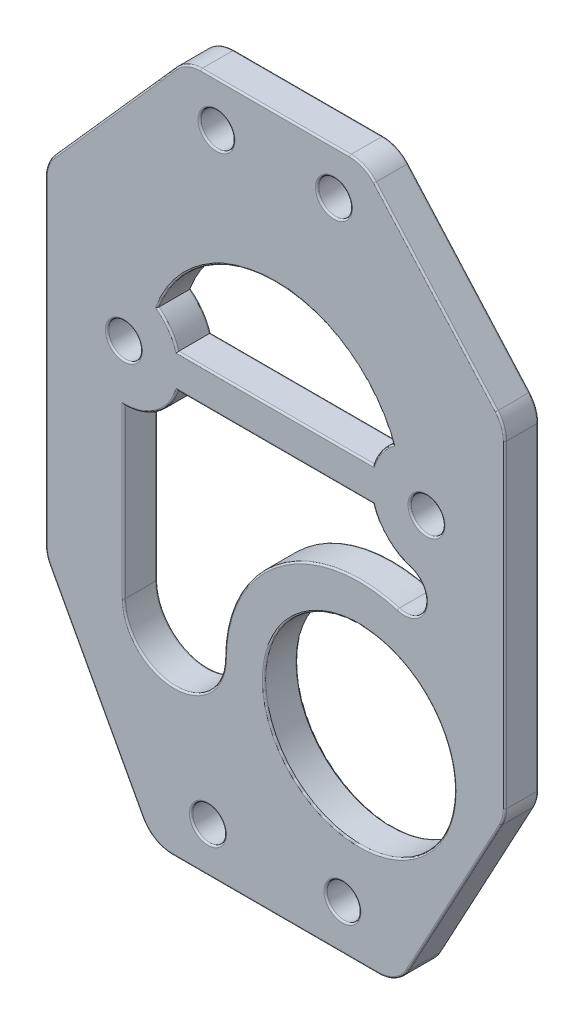
SolidWorks part; units mm, degrees
ref_plane "Front Plane" through (0, 0, 0) normal (0, 0, 1) x (1, 0, 0)
ref_plane "Top Plane" through (0, 0, 0) normal (0, 1, 0) x (1, 0, 0)
ref_plane "Right Plane" through (0, 0, 0) normal (1, 0, 0) x (0, 0, -1)
sketch "Sketch1" plane through (0, 0, 0) normal (0, 0, 1) x (1, 0, 0)
  line L0 (5.4616, 57.5405) -> (21.4413, 57.5405)
  line L1 (2.4515, -4.4595) -> (24.4515, -4.4595)
  line L2 (2.4515, -4.4595) -> (-7.0485, 13.1403)
  line L3 (-7.0485, 13.1403) -> (-7.0485, 43.4403)
  line L4 (-7.0485, 43.4403) -> (5.4616, 57.5405)
  line L5 (13.4515, 57.5405) -> (13.4515, -4.4595) construction
  line L6 (33.9515, 43.4403) -> (21.4413, 57.5405)
  line L7 (33.9515, 13.1403) -> (33.9515, 43.4403)
  line L8 (24.4515, -4.4595) -> (33.9515, 13.1403)
  line L9 (26.9515, 33.1403) -> (20.9515, 13.1403) construction
  line L14 (4.7212, 34.6403) -> (22.1818, 34.6403)
  line L16 (4.7212, 31.6403) -> (22.1818, 31.6403)
  line L20 (-0.0485, 28.1403) -> (-0.0485, 13.1403)
  circle A0 centre (-0.0485, 33.1403) radius 1.5
  circle A1 centre (7.4515, -0.4595) radius 1.5
  circle A2 centre (8.2116, 53.5405) radius 1.5
  circle A3 centre (18.6913, 53.5405) radius 1.5
  circle A4 centre (19.4515, -0.4595) radius 1.5
  circle A5 centre (26.9515, 33.1403) radius 1.5
  circle A6 centre (20.9515, 13.1403) radius 8.5
  arc A7 (24.3996, 24.6342) -> (8.9515, 13.1403) centre (20.9515, 13.1403) ccw
  arc A8 (-0.0485, 28.1403) -> (4.7212, 31.6403) centre (-0.0485, 33.1403) ccw
  arc A9 (25.5147, 28.3511) -> (22.1818, 31.6403) centre (26.9515, 33.1403) cw
  arc A10 (2.9372, 37.1509) -> (23.9657, 37.1509) centre (13.4515, 33.1403) cw
  arc A11 (24.3996, 24.6342) -> (25.5147, 28.3511) centre (24.9572, 26.4926) ccw
  arc A12 (-0.0485, 13.1403) -> (8.9515, 13.1403) centre (4.4515, 13.1403) ccw
  circle A13 centre (-0.0485, 33.1403) radius 5 construction
  circle A14 centre (26.9515, 33.1403) radius 5 construction
  circle A15 centre (20.9515, 13.1403) radius 12 construction
  arc A16 (4.7212, 34.6403) -> (2.9372, 37.1509) centre (-0.0485, 33.1403) ccw
  arc A17 (22.1818, 34.6403) -> (23.9657, 37.1509) centre (26.9515, 33.1403) cw
  dimension "D5" = 11
  dimension "D6" = 3
  dimension "D7" = 6
  dimension "D14" = 17
  dimension "D19" = 3
  dimension "D1" = 20
  dimension "D2" = 18.85
  dimension "D3" = 62
  dimension "D4" = 30.3
  dimension "D8" = 4
  dimension "D9" = 7
  dimension "D10" = 10.3
  dimension "D11" = 2.75
  dimension "D12" = 4
  dimension "D13" = 20.5
  dimension "D15" = 13
  dimension "D16" = 3.5
  dimension "D17" = 3.5
  dimension "D18" = 3.5
extrude "Boss-Extrude1" add sketch "Sketch1" along normal blind 3
fillet "Fillet1" radius 3 8 edges at (5.4616, 57.5405, 1.5) (21.4413, 57.5405, 1.5) (33.9515, 43.4403, 1.5) (33.9515, 13.1403, 1.5) (24.4515, -4.4595, 1.5) (2.4515, -4.4595, 1.5) (-7.0485, 13.1403, 1.5) (-7.0485, 43.4403, 1.5)
fillet "Fillet2" radius 0.15 68 edges at (29.4515, 13.1403, 0) (17.9515, -0.4595, 0) (22.8756, 36.0364, 0) (13.4515, 34.6403, 0) (4.0273, 36.0364, 0) (13.4515, 44.3935, 0) (9.7116, 53.5405, 0) (1.4515, 33.1403, 0) (-6.8532, 43.3661, 0) (-7.0485, 28.0997, 0) (-6.9571, 13.1633, 0) (-2.5436, 4.7944, 0) (2.7042, -4.0358, 0) (13.4515, -4.4595, 0) (24.1987, -4.0358, 0) (29.4465, 4.7944, 0) (33.8601, 13.1633, 0) (33.9515, 28.0997, 0) (33.7561, 43.3661, 0) (27.766, 50.4119, 0) (21.3226, 57.2767, 0) (13.4515, 57.5405, 0) (5.5803, 57.2767, 0) (-0.8631, 50.4119, 0) (13.7883, 22.7678, 0) (4.4515, 8.6403, 0) (-0.0485, 20.6403, 0) (2.9095, 29.1091, 0) (13.4515, 31.6403, 0) (23.4394, 29.5814, 0) (26.8156, 25.9351, 0) (8.9515, -0.4595, 0) (17.1913, 53.5405, 0) (25.4515, 33.1403, 0) (29.4515, 13.1403, 3) (25.4515, 33.1403, 3) (17.9515, -0.4595, 3) (17.1913, 53.5405, 3) (13.4515, 34.6403, 3) (22.8756, 36.0364, 3) (13.4515, 44.3935, 3) (4.0273, 36.0364, 3) (21.3226, 57.2767, 3) (27.766, 50.4119, 3) (33.7561, 43.3661, 3) (33.9515, 28.0997, 3) (33.8601, 13.1633, 3) (29.4465, 4.7944, 3) (24.1987, -4.0358, 3) (13.4515, -4.4595, 3) (2.7042, -4.0358, 3) (-2.5436, 4.7944, 3) (-6.9571, 13.1633, 3) (-7.0485, 28.0997, 3) (-6.8532, 43.3661, 3) (-0.8631, 50.4119, 3) (5.5803, 57.2767, 3) (13.4515, 57.5405, 3) (13.4515, 31.6403, 3) (2.9095, 29.1091, 3) (-0.0485, 20.6403, 3) (4.4515, 8.6403, 3) (13.7883, 22.7678, 3) (26.8156, 25.9351, 3) (23.4394, 29.5814, 3) (1.4515, 33.1403, 3) (8.9515, -0.4595, 3) (9.7116, 53.5405, 3)
